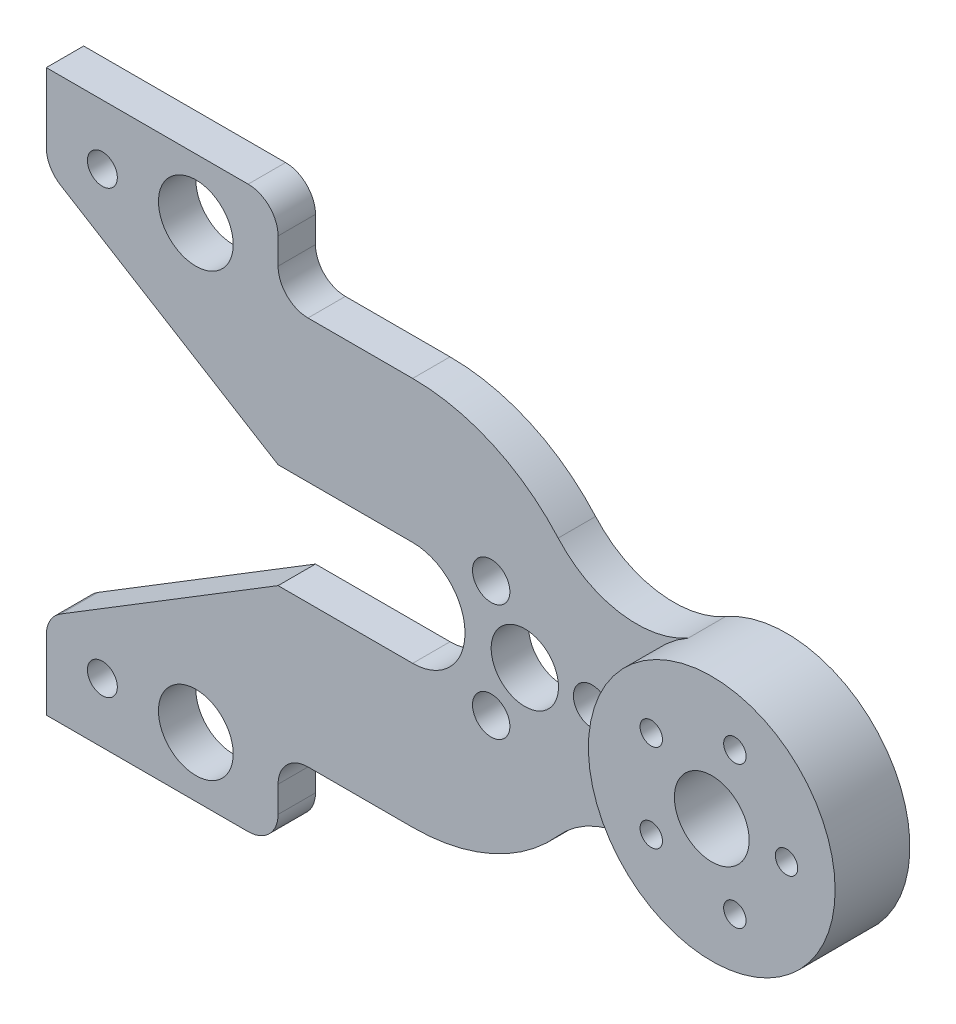
SolidWorks part; units mm, degrees
ref_plane "Спереди" through (0, 0, 0) normal (0, 0, 1) x (1, 0, 0)
ref_plane "Сверху" through (0, 0, 0) normal (0, 1, 0) x (1, 0, 0)
ref_plane "Справа" through (0, 0, 0) normal (1, 0, 0) x (0, 0, -1)
sketch "Эскиз1" plane through (0, 0, 0) normal (0, 0, 1) x (1, 0, 0)
  line L0 (33, 0) -> (-90, 0) construction
  line L1 (0, -33) -> (0, 0) construction
  line L3 (-184.1805, 49.659) -> (-191.8446, 54.3564) construction
  line L4 (-188, 75) -> (-134, 75)
  line L5 (-188, 75) -> (-188, 56.4798)
  line L6 (-90, 0) -> (-234.2858, 0) construction
  line L7 (-177, 59) -> (-126, 59) construction
  line L8 (-126, 14) -> (-90, 14)
  line L9 (-184.1805, 49.659) -> (-126, 14)
  line L10 (-118, 52) -> (-90, 52)
  line L11 (-126, 67) -> (-126, 60)
  line L12 (-188, 56.4798) -> (-188, 46.5503) construction
  line L13 (-126, -14) -> (-90, -14)
  line L14 (-118, -52) -> (-90, -52)
  line L15 (-184.1805, -49.659) -> (-126, -14)
  line L16 (-177, -59) -> (-126, -59) construction
  line L17 (-126, -67) -> (-126, -60)
  line L18 (-188, -75) -> (-134, -75)
  line L19 (-188, -75) -> (-188, -56.4798)
  circle A0 centre (0, 0) radius 33
  circle A1 centre (6.1803, 19.0211) radius 3
  circle A2 centre (20, 0) radius 3
  circle A3 centre (6.1803, -19.0211) radius 3
  circle A4 centre (-16.1803, -11.7557) radius 3
  circle A5 centre (-16.1803, 11.7557) radius 3
  circle A6 centre (0, 0) radius 10
  circle A7 centre (-173, 59) radius 4
  circle A8 centre (-148, 59) radius 10
  arc A9 (-90, -14) -> (-90, 14) centre (-90, 0) ccw
  arc A10 (-118, 52) -> (-126, 60) centre (-118, 60) cw
  arc A11 (-126, 67) -> (-134, 75) centre (-134, 67) ccw
  circle A12 centre (-60, 0) radius 9
  arc A13 (-51.0758, 34.4806) -> (-16.2926, 28.6976) centre (-30.1167, 53.047) ccw
  arc A14 (-51.0758, 34.4806) -> (-90, 52) centre (-90, 0) ccw
  arc A15 (-184.1805, 49.659) -> (-188, 56.4798) centre (-180, 56.4798) cw
  circle A16 centre (-42, 0) radius 5
  circle A17 centre (-69, -15.5885) radius 5
  circle A18 centre (-69, 15.5885) radius 5
  arc A19 (-51.0758, -34.4806) -> (-16.2926, -28.6976) centre (-30.1167, -53.047) cw
  arc A20 (-51.0758, -34.4806) -> (-90, -52) centre (-90, 0) cw
  arc A21 (-118, -52) -> (-126, -60) centre (-118, -60) ccw
  arc A22 (-184.1805, -49.659) -> (-188, -56.4798) centre (-180, -56.4798) ccw
  circle A23 centre (-173, -59) radius 4
  circle A24 centre (-148, -59) radius 10
  arc A25 (-126, -67) -> (-134, -75) centre (-134, -67) cw
  point P18 (0, 0)
  point P49 (-188, 52)
  point P55 (-60, 0)
  dimension "D1" = 66
  dimension "D3" = 6
  dimension "D5" = 5
  dimension "D6" = 188
  dimension "D10" = 8
  dimension "D12" = 25
  dimension "D13" = 20
  dimension "D17" = 8
  dimension "D7" = 8
  dimension "D18" = 14
  dimension "D21" = 28
  dimension "D22" = 52
  dimension "D23" = 30
  dimension "D24" = 18
  dimension "D15" = 8
  dimension "D25" = 18
  dimension "D27" = 10
  dimension "D28" = 20
  dimension "D4" = 20
  dimension "D8" = 75
  dimension "D9" = 59
  dimension "D11" = 15
  dimension "D14" = 14
  dimension "D16" = 52
  dimension "D19" = 90
  dimension "D20" = 62
  dimension "D29" = 52
  dimension "D26" = 3
extrude "Бобышка-Вытянуть1" add sketch "Эскиз1" along normal blind 10 contours A25 L17 A21 L14 A20 A19 A0 A13 A14 L10 A10 L11 A11 L4 L5 A15 L9 L8 A9 L13 L15 A22 L19 L18 A23 A18 A17 A16 A12 A8 A7 A24 region at (-161, 72.72, 0)
extrude "Бобышка-Вытянуть2" add sketch "Эскиз1<3>" along normal blind 20 contours A0 A6 A5 A4 A3 A2 A1 region at (16.1338, 27.7123, 0)
sketch "Эскиз1<3>" plane through (0, 0, 0) normal (0, 0, 1) x (1, 0, 0) same geometry as "Эскиз1"
